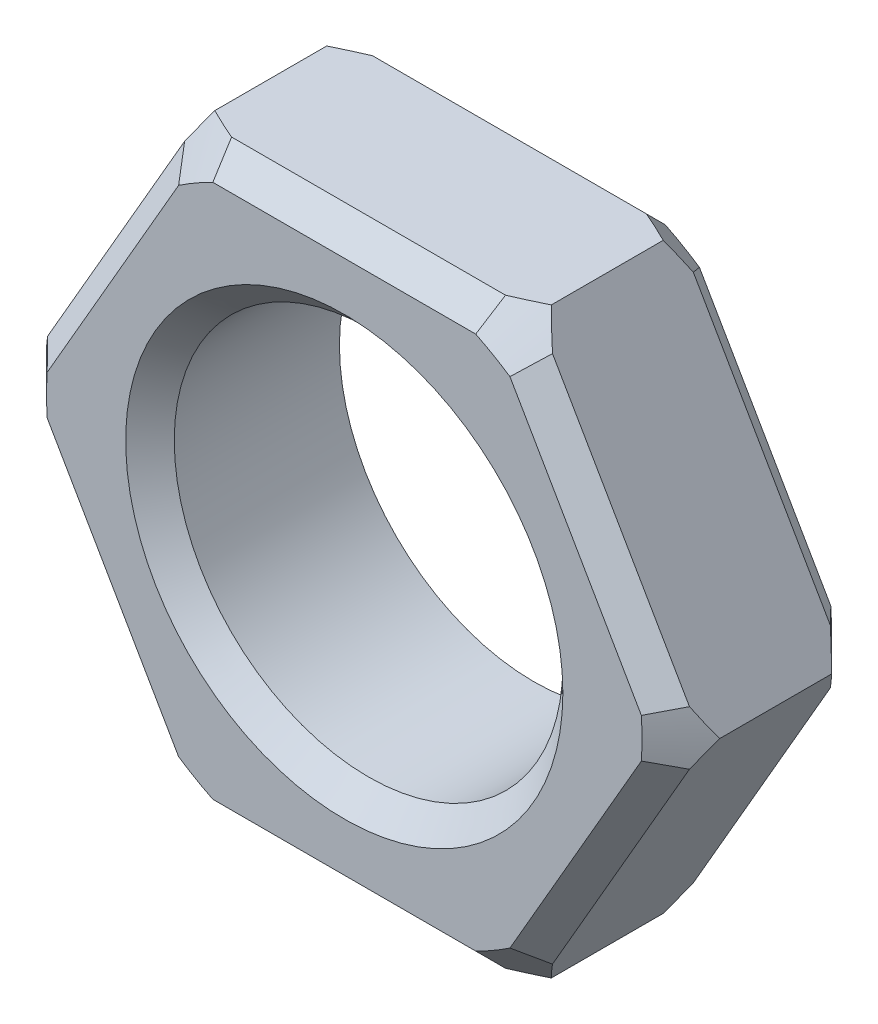
SolidWorks part; units mm, degrees
material "Легированная сталь (SS)"
ref_plane "Спереди" through (0, 0, 0) normal (0, 0, 1) x (1, 0, 0)
ref_plane "Сверху" through (0, 0, 0) normal (0, 1, 0) x (1, 0, 0)
ref_plane "Справа" through (0, 0, 0) normal (1, 0, 0) x (0, 0, -1)
sketch "Эскиз1" plane through (0, 0, 0) normal (0, 0, 1) x (1, 0, 0)
  line L1 (-6.9282, -12) -> (6.9282, -12)
  line L2 (6.9282, -12) -> (13.8564, 0)
  line L3 (13.8564, 0) -> (6.9282, 12)
  line L4 (6.9282, 12) -> (-6.9282, 12)
  line L5 (-6.9282, 12) -> (-13.8564, 0)
  line L6 (-13.8564, 0) -> (-6.9282, -12)
  circle A0 centre (0, 0) radius 12 construction
  circle A1 centre (0, 0) radius 8
  dimension "D1" = 24
  dimension "D2" = 16
extrude "Бобышка-Вытянуть1" add sketch "Эскиз1" along normal blind 7.8
chamfer "Фаска1" distance 1 angle 45 13 edges at (0, -12, 0) (10.3923, -6, 0) (10.3923, 6, 0) (0, 12, 0) (-10.3923, 6, 0) (-10.3923, -6, 0) (8, 0, 7.8) (-10.3923, 6, 7.8) (0, 12, 7.8) (10.3923, 6, 7.8) (10.3923, -6, 7.8) (0, -12, 7.8) (-10.3923, -6, 7.8)
sketch "Эскиз2" plane through (0, 0, 0) normal (0, 1, 0) x (1, 0, 0)
  line L0 (-11.3627, 0.8964) -> (-14.2591, -2)
  line L1 (-14.2591, -2) -> (-14.2591, -5.8)
  line L2 (-14.2591, -5.8) -> (-11.6153, -8.4438)
  line L3 (-11.6153, -8.4438) -> (-16.6988, -8.4438)
  line L4 (-16.6988, -8.4438) -> (-16.6988, 0.8964)
  line L5 (-16.6988, 0.8964) -> (-11.3627, 0.8964)
  line L6 (-6.3509, -7.8) -> (-12.7017, -7.8) construction
  line L7 (-12.7017, 0) -> (-6.3509, 0) construction
  line L8 (0, 2.1899) -> (0, -8.9342) construction
  dimension "D1" = 45
  dimension "D2" = 45
  dimension "D3" = 2
  dimension "D4" = 2
revolve "Вырез-Повернуть1" cut sketch "Эскиз2" angle 360 about L8
